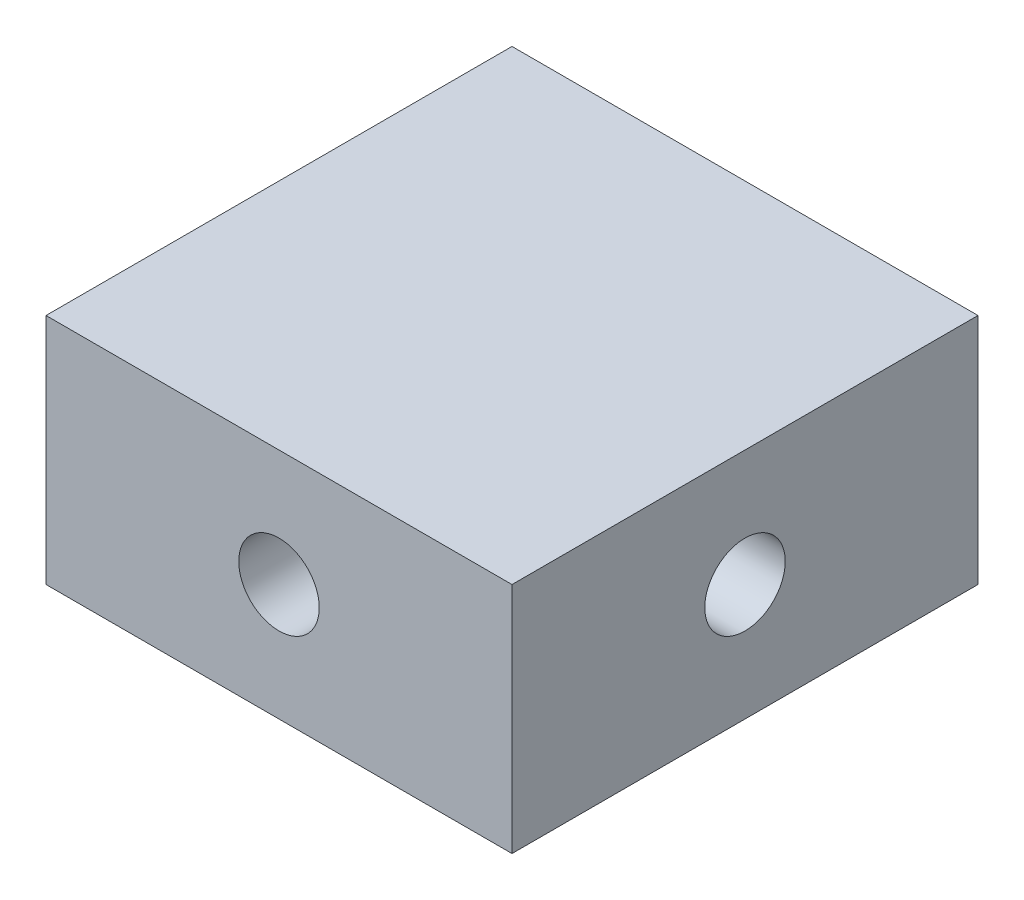
SolidWorks part; units mm, degrees
material "ABS"
ref_plane "Front Plane" through (0, 0, 0) normal (0, 0, 1) x (1, 0, 0)
ref_plane "Top Plane" through (0, 0, 0) normal (0, 1, 0) x (1, 0, 0)
ref_plane "Right Plane" through (0, 0, 0) normal (1, 0, 0) x (0, 0, -1)
sketch "Sketch1" plane through (0, 0, 0) normal (0, 1, 0) x (1, 0, 0)
  line L7 (-10, -10) -> (10, -10)
  line L8 (-10, -10) -> (-10, 10)
  line L9 (-10, 10) -> (10, 10)
  line L10 (10, -10) -> (10, 10)
  line L11 (-10, -10) -> (10, 10) construction
  line L12 (-10, 10) -> (10, -10) construction
  point P1 (0, 0)
  point P2 (0, 0)
  point P6 (0, 0)
  dimension "D1" = 20
  dimension "D2" = 20
extrude "Boss-Extrude1" add sketch "Sketch1" along normal mid plane 10 contours L7 L10 L8 | L10 L8 | L8 | L10 | L10 L9 L8 region at (0, 0, 0)
hole_wizard "#8-32 Tapped Hole1" positions "Sketch2" profile "Sketch3" tap size "#8-32" standard "ANSI Inch"
sketch "Sketch2" plane through (10, 0, 0) normal (1, 0, 0) x (0, 0, -1)
  point P0 (0, 0)
sketch "Sketch3" plane through (10, 0, 0) normal (0, 1, 0) x (0, 0, -1)
  line L0 (0, 0) -> (0, 7.3878)
  line L1 (0, 7.3878) -> (1.7272, 6.35)
  line L2 (1.7272, 6.35) -> (1.7272, 0)
  line L5 (1.7272, 0) -> (0, 0)
  line L10 (0, 7.3878) -> (-1.7272, 6.35) construction
  line L11 (0, -6.35) -> (0, 107.95) construction
  dimension "Tap Drill Dia." = 3.4544
  dimension "Tap Drill Depth" = 6.35
  dimension "Drill Angle" = 118
cosmetic thread "Hole Thread5" [suppressed] parameters "D1"=8.33, "D2"=4.4544
ref_axis "Axis1" through (0, 0, 0) along (0, 1, 0)
pattern_circular "CirPattern1" count 4 over 360 about axis through (0, 0, 0) along (0, 1, 0) of "#8-32 Tapped Hole1"
cosmetic thread "Hole Thread6" [suppressed] parameters "D1"=8.33, "D2"=4.4544
cosmetic thread "Hole Thread7" [suppressed] parameters "D1"=8.33, "D2"=4.4544
cosmetic thread "Hole Thread8" [suppressed] parameters "D1"=8.33, "D2"=4.4544
fillet "Fillet1" [suppressed] radius 5
